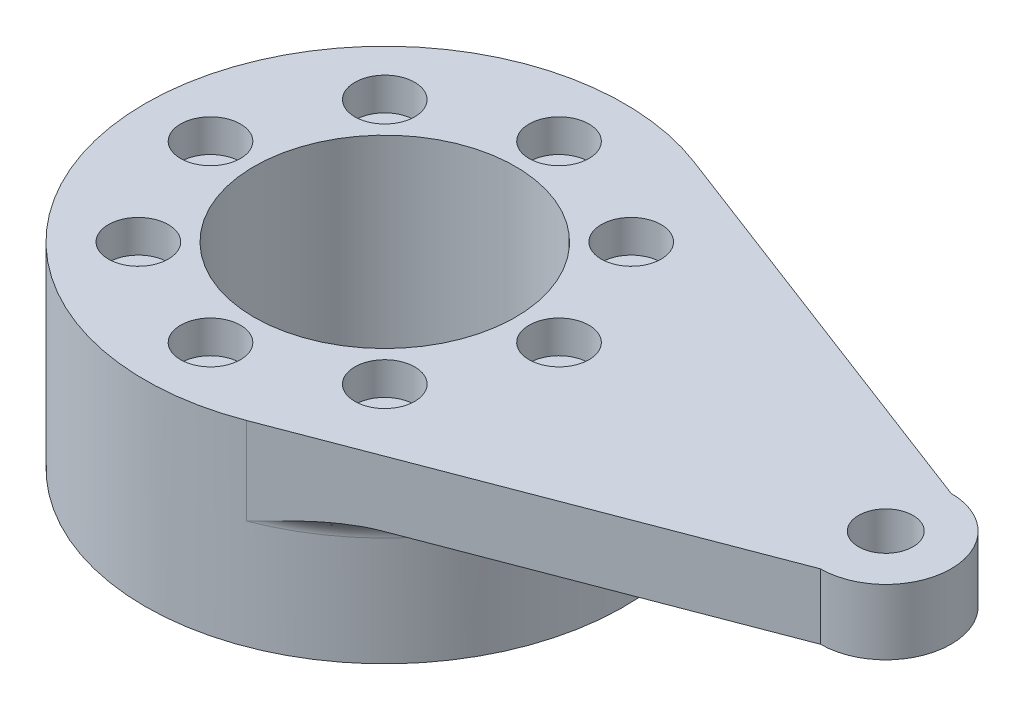
SolidWorks part; units mm, degrees
material "6061 合金"
ref_plane "前视基准面" through (0, 0, 0) normal (0, 0, 1) x (1, 0, 0)
ref_plane "上视基准面" through (0, 0, 0) normal (0, 1, 0) x (1, 0, 0)
ref_plane "右视基准面" through (0, 0, 0) normal (1, 0, 0) x (0, 0, -1)
sketch "草图1" plane through (0, 0, 0) normal (0, 1, 0) x (1, 0, 0)
  circle A0 centre (0, 0) radius 22
  circle A1 centre (0, 0) radius 16 construction
  circle A2 centre (-16, 0) radius 1.5
  circle A4 centre (-11.3137, 11.3137) radius 1.5
  circle A6 centre (0, 16) radius 1.5
  circle A8 centre (11.3137, 11.3137) radius 1.5
  circle A10 centre (16, 0) radius 1.5
  circle A12 centre (11.3137, -11.3137) radius 1.5
  circle A14 centre (0, -16) radius 1.5
  circle A16 centre (-11.3137, -11.3137) radius 1.5
  circle A18 centre (-14.7821, 6.1229) radius 1.5 [skipped]
  circle A19 centre (-6.1229, 14.7821) radius 1.5 [skipped]
  circle A20 centre (6.1229, 14.7821) radius 1.5 [skipped]
  circle A21 centre (14.7821, 6.1229) radius 1.5 [skipped]
  circle A22 centre (14.7821, -6.1229) radius 1.5 [skipped]
  circle A23 centre (6.1229, -14.7821) radius 1.5 [skipped]
  circle A24 centre (-6.1229, -14.7821) radius 1.5 [skipped]
  circle A25 centre (-14.7821, -6.1229) radius 1.5 [skipped]
  point P39 (0, 0)
  dimension "D1" = 16
extrude "凸台-拉伸1" add sketch "草图1" along normal blind 12
sketch "草图3" plane through (0, 12, 0) normal (0, 1, 0) x (1, 0, 0)
  line L0 (0, 0) -> (35.7311, 0) construction
  line L1 (46, -6) -> (7.8406, -20.5554)
  line L2 (46, 6) -> (7.8406, 20.5554)
  circle A0 centre (0, 0) radius 22
  circle A1 centre (0, 0) radius 22
  circle A2 centre (0, 0) radius 22
  circle A3 centre (46, 0) radius 6
  circle A4 centre (46, 0) radius 2.5
  point P14 (0, 0)
  circle M3 centre (0, -16) radius 1.5
  circle M4 centre (16, 0) radius 1.5
  circle M5 centre (0, 16) radius 1.5
  circle M6 centre (-16, 0) radius 1.5
  circle M7 centre (0, 0) radius 22
  circle M8 centre (-11.3137, 11.3137) radius 1.5
  circle M9 centre (11.3137, 11.3137) radius 1.5
  circle M10 centre (11.3137, -11.3137) radius 1.5
  circle M11 centre (-11.3137, -11.3137) radius 1.5
  dimension "D1" = 0
extrude "凸台-拉伸2" add sketch "草图3" along normal blind 6 contours A2 L0 A3 L2 | L0 A2 M7 M6 M4 M5 M9 M8 | L0 A2 M7 M4 M6 M10 M11 M3 | L0 L1 A3 M7 | A3 L0 A4 | L0 A3 A4 region at (17.6051, 12, 12.1271) region at (18.5795, 12, -12.7983) region at (50.1226, 12, -4.1226)
sketch "草图2" plane through (0, 0, 0) normal (0, -1, 0) x (1, 0, 0)
  circle A0 centre (-16, 0) radius 1.5 construction
  circle A1 centre (0, 0) radius 22
  circle A2 centre (0, 0) radius 22
  circle A4 centre (0, 0) radius 16 construction
  circle A6 centre (-14.7821, 6.1229) radius 2.05
  circle A10 centre (6.1229, 14.7821) radius 2.05
  circle A14 centre (14.7821, -6.1229) radius 2.05
  circle A18 centre (-6.1229, -14.7821) radius 2.05
  point P40 (0, 0)
  dimension "D1" = 0
extrude "切除-拉伸1" cut sketch "草图2" against normal blind 3.5 contours A18 | A6 | A14 | A10 region at (-14.7821, 0, 6.1229) region at (6.1229, 0, 14.7821) region at (14.7821, 0, -6.1229) region at (-6.1229, 0, -14.7821)
sketch "草图4" plane through (0, 18, 0) normal (0, 1, 0) x (1, 0, 0)
  line L2 (7.8406, -20.5554) -> (46, -6)
  line L3 (46, 6) -> (7.8406, 20.5554)
  line L4 (7.8406, -20.5554) -> (46, -6)
  line L5 (46, 6) -> (7.8406, 20.5554)
  circle A0 centre (0, 0) radius 16 construction
  circle A1 centre (-16, 0) radius 2.75
  arc A2 (46, -6) -> (46, 6) centre (46, 0) ccw
  arc A3 (7.8406, 20.5554) -> (7.8406, -20.5554) centre (0, 0) ccw
  arc A4 (46, -6) -> (46, 6) centre (46, 0) ccw
  arc A5 (7.8406, 20.5554) -> (7.8406, -20.5554) centre (0, 0) ccw
  circle A6 centre (-11.3137, 11.3137) radius 2.75
  circle A7 centre (0, 16) radius 2.75
  circle A8 centre (11.3137, 11.3137) radius 2.75
  circle A9 centre (16, 0) radius 2.75
  circle A10 centre (11.3137, -11.3137) radius 2.75
  circle A11 centre (0, -16) radius 2.75
  circle A12 centre (-11.3137, -11.3137) radius 2.75
  point P26 (0, 0)
  circle M5 centre (-16, 0) radius 1.5
  circle M6 centre (16, 0) radius 1.5
  circle M12 centre (0, 16) radius 1.5
  circle M13 centre (11.3137, 11.3137) radius 1.5
  circle M14 centre (-11.3137, 11.3137) radius 1.5
  circle M15 centre (11.3137, -11.3137) radius 1.5
  circle M16 centre (-11.3137, -11.3137) radius 1.5
  circle M17 centre (0, -16) radius 1.5
  dimension "D1" = 0
extrude "切除-拉伸2" cut sketch "草图4" against normal blind 3 contours A1 M5 | A12 M16 | A6 M14 | A7 M12 | A8 M13 | A9 M6 | A10 M15 | A11 M17 region at (-18.6722, 18, 0) region at (-13.9859, 18, -11.3137) region at (-2.6722, 18, -16) region at (8.6415, 18, -11.3137) region at (13.3278, 18, 0) region at (8.6415, 18, 11.3137) region at (-2.6722, 18, 16) region at (-13.9859, 18, 11.3137)
sketch "草图5" plane through (0, 18, 0) normal (0, 1, 0) x (1, 0, 0)
  line L2 (7.8406, -20.5554) -> (46, -6)
  line L3 (46, 6) -> (7.8406, 20.5554)
  line L4 (7.8406, -20.5554) -> (46, -6)
  line L5 (46, 6) -> (7.8406, 20.5554)
  circle A0 centre (0, 0) radius 12
  arc A2 (46, -6) -> (46, 6) centre (46, 0) ccw
  arc A3 (7.8406, 20.5554) -> (7.8406, -20.5554) centre (0, 0) ccw
  arc A4 (46, -6) -> (46, 6) centre (46, 0) ccw
  arc A5 (7.8406, 20.5554) -> (7.8406, -20.5554) centre (0, 0) ccw
  dimension "D1" = 0
extrude "切除-拉伸3" cut sketch "草图5" against normal through all contours A0 region at (0, 18, 0)
fillet "圆角1" radius 2 1 edges at (22, 12, 0)
